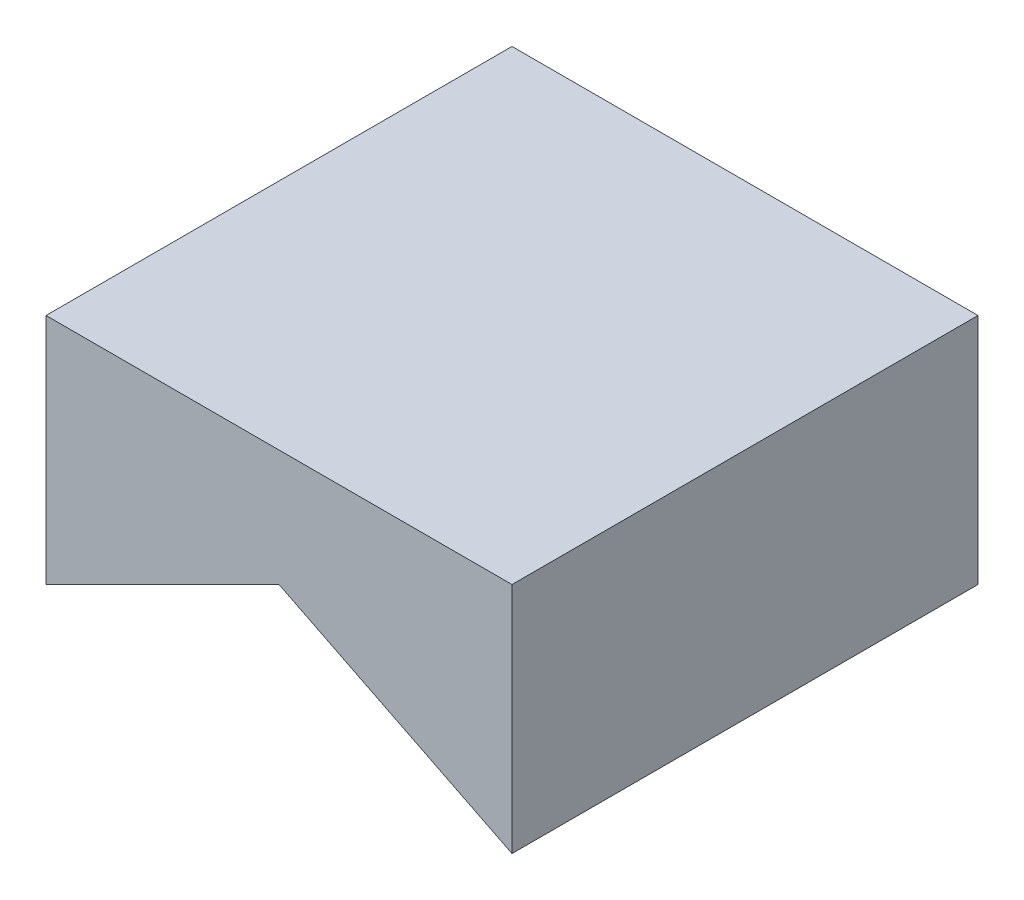
SolidWorks part; units mm, degrees
material "Pine"
ref_plane "Front Plane" through (0, 0, 0) normal (0, 0, 1) x (1, 0, 0)
ref_plane "Top Plane" through (0, 0, 0) normal (0, 1, 0) x (1, 0, 0)
ref_plane "Right Plane" through (0, 0, 0) normal (1, 0, 0) x (0, 0, -1)
sketch "Sketch2" plane through (0, 0, 0) normal (0, 0, 1) x (1, 0, 0)
  line L0 (-50.8, -25.4) -> (0, 0)
  line L2 (-50.8, -25.4) -> (-50.8, 25.4)
  line L3 (-50.8, 25.4) -> (50.8, 25.4)
  line L4 (50.8, -25.4) -> (50.8, 25.4)
  line L5 (-50.8, -25.4) -> (50.8, 25.4) construction
  line L6 (-50.8, 25.4) -> (50.8, -25.4) construction
  line L7 (0, 0) -> (50.8, -25.4)
  point P0 (0, 0)
  dimension "D1" = 101.6
  dimension "D2" = 50.8
extrude "Boss-Extrude2" add sketch "Sketch2" along normal blind 101.6
sketch "Sketch3" plane through (0, 0, 0) normal (0.4472, -0.8944, 0) x (0.8944, 0.4472, 0)
  line L0 (-56.7961, 101.6) -> (0, 0) construction
  line L1 (-56.7961, 50.8) -> (0, 50.8) construction
  line L2 (-56.7961, 101.6) -> (-56.7961, 0) construction
  line L3 (0, 101.6) -> (0, 0) construction
  line L4 (-10.8958, 42.8219) -> (-45.9003, 42.8219)
  line L5 (-10.8958, 42.8219) -> (-10.8958, 58.7781)
  line L6 (-45.9003, 42.8219) -> (-45.9003, 58.7781)
  line L7 (-10.8958, 58.7781) -> (-45.9003, 58.7781)
  line L8 (-10.8958, 42.8219) -> (-45.9003, 58.7781) construction
  line L9 (-45.9003, 42.8219) -> (-10.8958, 58.7781) construction
  point P11 (-28.3981, 50.8)
extrude "Cut-Extrude1" cut sketch "Sketch3" against normal blind 19.05
sketch "Sketch5" plane through (0, 0, 0) normal (-0.4472, -0.8944, 0) x (0.8944, -0.4472, 0)
  line L0 (0, 101.6) -> (56.7961, 0) construction
  line L1 (56.7961, 50.8) -> (28.3981, 50.8) construction
  line L2 (56.7961, 101.6) -> (56.7961, 0) construction
  line L3 (12.5231, 42.5637) -> (44.2731, 42.5637)
  line L4 (12.5231, 42.5637) -> (12.5231, 59.0363)
  line L5 (44.2731, 42.5637) -> (44.2731, 59.0363)
  line L6 (12.5231, 59.0363) -> (44.2731, 59.0363)
  line L7 (12.5231, 42.5637) -> (44.2731, 59.0363) construction
  line L8 (44.2731, 42.5637) -> (12.5231, 59.0363) construction
  dimension "D1" = 31.75
extrude "Cut-Extrude2" cut sketch "Sketch5" against normal blind 19.05
sketch "Sketch6" plane through (0, 25.4, 0) normal (0, 1, 0) x (1, 0, 0)
  line L0 (0, 0) -> (0, -101.6) construction
  line L1 (50.8, 0) -> (-50.8, 0) construction
  line L2 (50.8, -101.6) -> (-50.8, -101.6) construction
